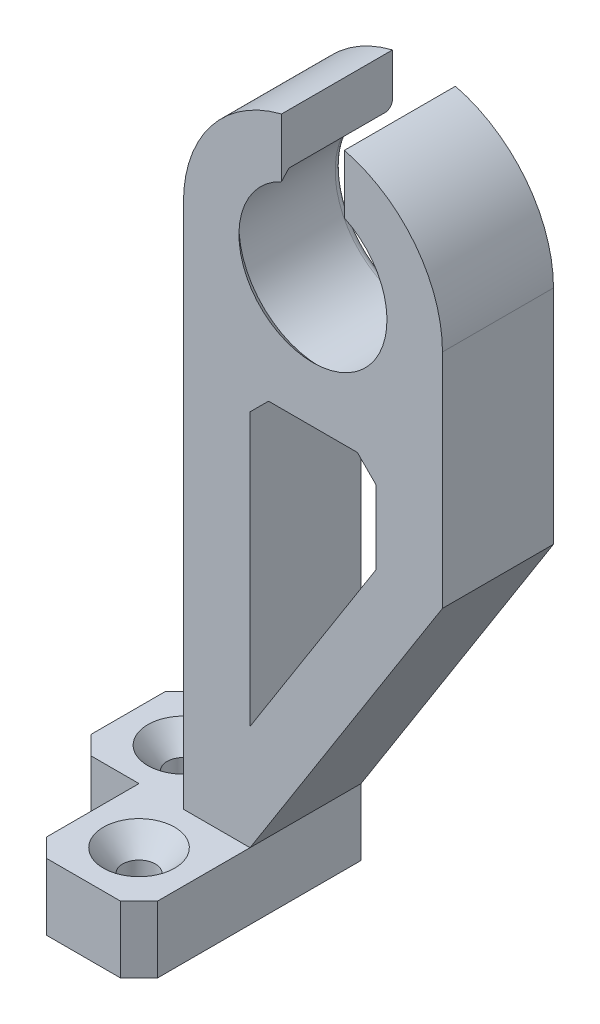
SolidWorks part; units mm, degrees
ref_plane "Front Plane" through (0, 0, 0) normal (0, 0, 1) x (1, 0, 0)
ref_plane "Top Plane" through (0, 0, 0) normal (0, 1, 0) x (1, 0, 0)
ref_plane "Right Plane" through (0, 0, 0) normal (1, 0, 0) x (0, 0, -1)
sketch "Sketch1" plane through (0, 0, 0) normal (0, 0, 1) x (1, 0, 0)
  line L0 (17.5, 0) -> (-17.5, 0)
  line L9 (-8.5, -17.5) -> (8.5, -17.5)
  line L22 (-8.5, -17.5) -> (-8.5, -80)
  line L23 (0, 0) -> (0, -17.5) construction
  line L24 (-4.25, 7.5) -> (4.25, 7.5)
  line L31 (-4.25, 7.5) -> (-4.25, 17.5)
  line L32 (-4.25, 17.5) -> (4.25, 17.5)
  line L33 (4.25, 17.5) -> (4.25, 7.5)
  line L35 (8.5, -17.5) -> (8.5, -30)
  line L36 (17.5, -30) -> (17.5, 0)
  line L37 (8.5, -30) -> (17.5, -30)
  line L44 (17.5, -30) -> (-8.5, -71)
  line L45 (-17.5, -71) -> (-17.5, 0)
  line L46 (-32.5, -80) -> (-8.5, -80)
  line L48 (8.5, -30) -> (-8.5, -56.8077)
  line L51 (-17.5, -71) -> (-32.5, -71)
  line L52 (-32.5, -80) -> (-32.5, -71)
  circle A0 centre (0, 0) radius 17.5
  circle A1 centre (0, 0) radius 11
  point P4 (0, 0)
  point P31 (0, 11)
  point P38 (0, 7.5)
  dimension "D2" = 22
  dimension "D3" = 35
  dimension "D4" = 80
  dimension "D5" = 9
  dimension "D6" = 9
  dimension "D7" = 15
  dimension "D8" = 30
  dimension "D10" = 8.5
  dimension "D11" = 10
extrude "Boss-Extrude1" add sketch "Sketch1" along normal blind 15 contours L23 A1 L0 A0 | A1 L31 A0 L0 | A1 L0 A0 L33 | A1 L23 A0 L0 | A0 L45 L37 L22 L9 | A0 L9 L35 L37 L36 | L52 L45 L51 | L37 L48 L22 L44 region at (9.2291, -9.2291, 0) region at (13.218, -20.0037, 0) region at (10.9238, 8.0835, 0) region at (2.407, -47.1995, 0) region at (-9.2291, -9.2291, 0) region at (-15.1735, -50.454, 0) region at (-10.9238, 8.0835, 0)
ref_plane "Plane1" through (-25, 0, 0) normal (1, 0, 0) x (0, 0, -1)
sketch "Sketch6" plane through (0, 0, 15) normal (0, 0, -1) x (-1, 0, 0)
  line L0 (-4.25, 10.1458) -> (-4.25, 9.0519)
  line L5 (4.25, 10.1458) -> (4.25, 9.0519)
  line L6 (4.25, 10.1458) -> (4.25, 16.9761) construction
  line L7 (-4.25, 16.9761) -> (-4.25, 10.1458) construction
  circle A0 centre (0, 0) radius 11
  arc A1 (-4.25, 10.1458) -> (4.25, 10.1458) centre (0, 0) ccw construction
  circle A2 centre (0, 0) radius 10
  arc M68 (-4.25, 10.1458) -> (4.25, 10.1458) centre (0, 0) ccw
  dimension "D1" = 1
extrude "Boss-Extrude3" add sketch "Sketch6" along normal blind 1 contours L0 A2 L5 M68 region at (4.5551, 9.5989, 15)
sketch "Sketch7" plane through (0, 0, 15) normal (0, 0, 1) x (1, 0, 0)
  line L0 (-32.5, -80) -> (-8.5, -80) construction
  line L1 (-23.5, -71) -> (-8.5, -71)
  line L2 (-23.5, -71) -> (-23.5, -80)
  line L3 (-23.5, -80) -> (-8.5, -80)
  line L4 (-8.5, -71) -> (-8.5, -80)
  line L5 (-8.5, -71) -> (-8.5, -80) construction
  line L6 (-17.5, -71) -> (-32.5, -71) construction
  dimension "D1" = 15
extrude "Boss-Extrude4" add sketch "Sketch7" along normal blind 15
ref_plane "Plane3" through (-25, 0, 0) normal (-1, 0, 0) x (0, 0, 1)
sketch "Sketch11" plane through (-25, 0, 0) normal (-1, 0, 0) x (0, 0, 1)
  line L0 (7.5, -71) -> (7.5, -80)
  line L3 (7.5, -71) -> (12.3079, -71)
  line L4 (12.3079, -71) -> (9.7, -74)
  line L5 (9.7, -74) -> (9.7, -80)
  line L6 (9.7, -80) -> (7.5, -80)
  line L7 (9.7, -74) -> (7.5, -74) construction
  line L8 (15, -71) -> (0, -71) construction
  line L9 (15, -71) -> (0, -71) construction
  line L10 (15, -80) -> (0, -80) construction
  dimension "D1" = 3
  dimension "D2" = 131
  dimension "D3" = 2.2
revolve "Cut-Revolve4" cut sketch "Sketch11" angle 360 about L0
ref_plane "Plane2" through (0, 0, 22.5) normal (0, 0, 1) x (1, 0, 0)
sketch "Sketch10" plane through (0, 0, 22.5) normal (0, 0, 1) x (1, 0, 0)
  line L0 (-16, -71) -> (-11.1921, -71)
  line L1 (-8.5, -71) -> (-23.5, -71) construction
  line L2 (-11.1921, -71) -> (-13.8, -74)
  line L3 (-13.8, -74) -> (-13.8, -80)
  line L4 (-23.5, -80) -> (-8.5, -80) construction
  line L5 (-13.8, -80) -> (-16, -80)
  line L6 (-16, -80) -> (-16, -71)
  line L7 (-13.8, -74) -> (-16, -74) construction
  dimension "D1" = 3
  dimension "D2" = 2.2
  dimension "D3" = 131
revolve "Cut-Revolve3" cut sketch "Sketch10" angle 360 about L6
fillet "Fillet1" radius 1 1 edges at (0, -11, 0)
chamfer "Chamfer1" distance 2.5 angle 45 6 edges at (-8.5, -17.5, 7.5) (-8.5, -75.5, 30) (-23.5, -75.5, 30) (8.5, -17.5, 7.5) (-32.5, -75.5, 15) (-32.5, -75.5, 0)
chamfer "Chamfer2" distance 1 angle 45 1 edges at (0, -10, 14)
